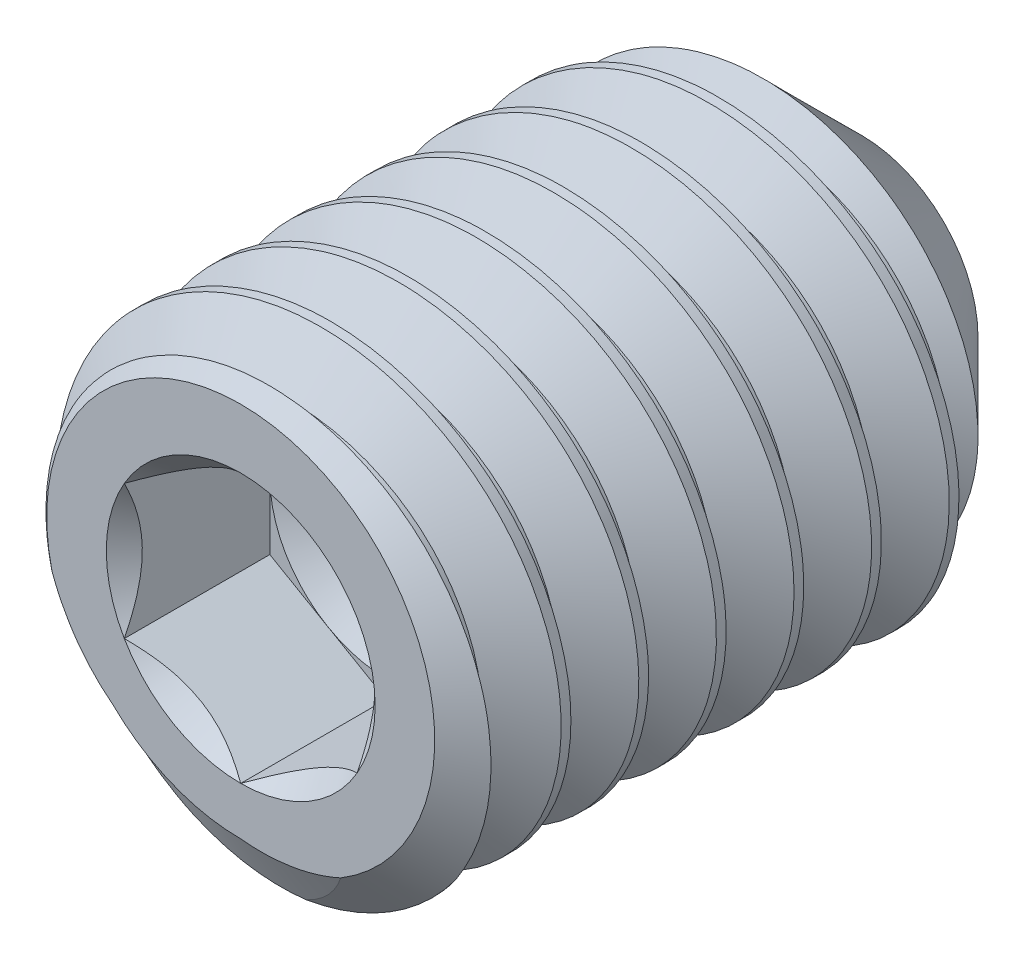
SolidWorks part; units mm, degrees
other "Imported1" parameters "D3"=4.4, "D1"=46.842, "Length"=4, "Drive Size"=1.5, "Thread Size"=3, "Thread Pitch"=0.5, "D2"=0.0866, "hex Depth"=0.9375, "Dia"=12, "D4"=2.3829, "Cup Point Dia"=3.3528, "D5"=1.436, "D6"=1.4986, "D7"=5.0014, "Pitch"=1.75
ref_plane "Front" through (0, 0, 0) normal (0, 0, 1) x (1, 0, 0)
ref_plane "Top" through (0, 0, 0) normal (0, 1, 0) x (1, 0, 0)
ref_plane "Right" through (0, 0, 0) normal (1, 0, 0) x (0, 0, -1)
sketch "Sketch1" plane through (0, 0, 0) normal (1, 0, 0) x (0, 0, -1)
  line L0 (2, 1.5) -> (-2, 1.5) construction
  line L1 (-2, 1.5) -> (-2, -1.5) construction
  line L2 (-2, -1.5) -> (2, -1.5) construction
  line L3 (2, -1.5) -> (2, 1.5) construction
  line L4 (-2, 0.75) -> (-2, -0.75) construction
  line L5 (1.9688, 1.5541) -> (2.4688, 1.5541) construction
  line L6 (1.9688, 1.5541) -> (2, 1.5) construction
  line L7 (2, 1.5) -> (2.4375, 1.5) construction
  line L8 (2.4375, 1.5) -> (2.4688, 1.5541) construction
  line L9 (2, 1.5) -> (2.2188, 1.1211) construction
  line L10 (2.2188, 1.1211) -> (2.4375, 1.5) construction
  line L11 (2.1875, 1.1752) -> (2.25, 1.1752) construction
  line L12 (2.2188, 1.5541) -> (2.2188, 1.5) construction
  line L13 (2.2188, 1.1752) -> (2.2188, 1.1211) construction
  point P3 (0, 1.5)
  point P24 (-2, 0)
  point P25 (-2, 0)
  dimension "D1" = 0.0625
sketch "Sketch11" plane through (0, 0, 0) normal (1, 0, 0) x (0, 0, -1)
  line L0 (-2, 0) -> (-2, 1.25)
  line L1 (-2, 1.25) -> (-1.8249, 1.5)
  line L2 (-1.8249, 1.5) -> (1.25, 1.5)
  line L3 (1.25, 1.5) -> (2, 0.75)
  line L4 (2, 0.75) -> (1.5494, 0)
  line L5 (1.5494, 0) -> (-2, 0)
  line L6 (1.5494, 0) -> (2, 0) construction
  line L7 (2, 0) -> (2, 0.75) construction
  line L8 (2, -0.75) -> (1.5494, 0) construction
  line L9 (-1.8249, -1.5) -> (1.25, -1.5) construction
  line L10 (-2, -1.5) -> (2, -1.5) construction
  line L11 (-2, 1.5) -> (-2, -1.5) construction
  line L12 (2, -1.5) -> (2, 1.5) construction
  point P11 (0.25, -1.5)
  point P12 (-2, 1.5)
  dimension "D3" = 35
  dimension "D5" = 118
  dimension "D6" = 45
  dimension "D1" = 0.25
  dimension "D2" = 1.75
  dimension "D4" = 0.75
revolve "Revolve1" add sketch "Sketch11" angle 360 about L6
sketch "Sketch2" plane through (0, 0, 2) normal (0, 0, 1) x (1, 0, 0)
  line L1 (0, 0.866) -> (-0.75, 0.433)
  line L2 (-0.75, 0.433) -> (-0.75, -0.433)
  line L3 (-0.75, -0.433) -> (0, -0.866)
  line L4 (0, -0.866) -> (0.75, -0.433)
  line L5 (0.75, -0.433) -> (0.75, 0.433)
  line L6 (0.75, 0.433) -> (0, 0.866)
  circle A0 centre (0, 0) radius 0.75 construction
  circle A1 centre (0, 0) radius 1.5 construction
extrude "Cut-Extrude1" cut sketch "Sketch2" against normal blind 0.9375
sketch "Sketch3" plane through (0, 0, 2) normal (0, 0, 1) x (1, 0, 0)
  circle A0 centre (0, 0) radius 0.866
extrude "Cut-Extrude2" cut sketch "Sketch3" against normal through all draft 45
sketch "Sketch4" plane through (0, 0, 1.0625) normal (0, 0, 1) x (1, 0, 0)
  circle A0 centre (0, 0) radius 0.75 construction
  circle A1 centre (0, 0) radius 0.75
extrude "Cut-Extrude3" cut sketch "Sketch4" against normal through all draft 60
sketch "Sketch13" plane through (0, 0, 0) normal (1, 0, 0) x (0, 0, -1)
  line L0 (0, -1.5) -> (0, 1.5) construction
  line L2 (-1.8249, 1.5) -> (1.25, 1.5) construction
  line L4 (1.5494, 0) -> (-2, 0) construction
  point P0 (-1.4506, 0)
  point P4 (0, 0)
  point P9 (1.4506, 0)
  dimension "D1" = 3
ref_plane "Plane1" through (0, 0, -2) normal (0, 0, 1) x (1, 0, 0)
sketch "Sketch5" plane through (0, 0, -2) normal (0, 0, 1) x (1, 0, 0)
  circle A0 centre (0, 0) radius 1.5 construction
  circle A1 centre (0, 0) radius 1.5
curve "Helix/Spiral1" pitch 0.5 height 4.4 radius 1.5 centre (0, 0, -2) axis (0, 0, 1) start towards (0, 1, 0)
sketch "Sketch6" plane through (0, 0, 0) normal (1, 0, 0) x (0, 0, -1)
  line L0 (1.9844, 1.5271) -> (2.4531, 1.5271)
  line L1 (1.9688, 1.5541) -> (2, 1.5) construction
  line L2 (2.4375, 1.5) -> (2.4688, 1.5541) construction
  line L3 (2.4531, 1.5271) -> (2.25, 1.1752)
  line L4 (2.25, 1.1752) -> (2.1875, 1.1752)
  line L5 (2.1875, 1.1752) -> (1.9844, 1.5271)
sweep "Cut-Sweep1" cut profiles "Sketch6" path "Helix/Spiral1"
equation "\"D3@Helix/Spiral1\" = \"Length@Sketch1\" * 1.1"
equation "\"hex Depth@Cut-Extrude1\"=\"Drive Size@Sketch1\" * .625"
equation "\"D1@Sketch11\" = \"Thread Pitch@Sketch1\" * .5"
equation "\"D2@Sketch11\" = \"Thread Pitch@Sketch1\" * 3.5"
equation "\"D1@Helix/Spiral1\" = \"Thread Pitch@Sketch1\""
equation "\"D4@Sketch11\" = \"Thread Pitch@Sketch1\" * 1.5"
equation "\"D1@Sketch1\" = \"Thread Pitch@Sketch1\" / 8"
equation "\"D1@Sketch13\"=\"Thread Size@Sketch1\""
